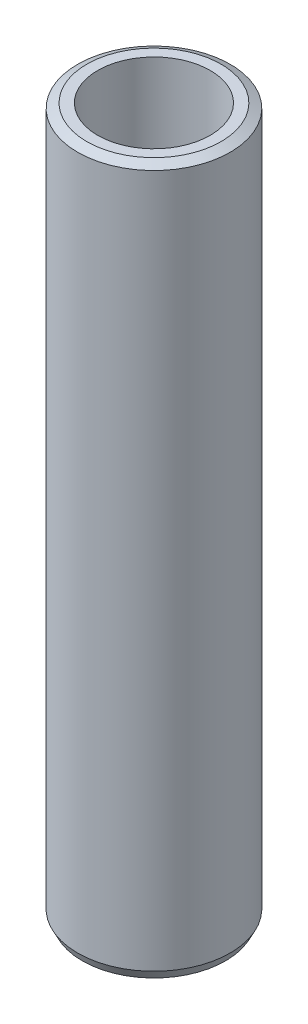
SolidWorks part; units mm, degrees
ref_plane "Front Plane" through (0, 0, 0) normal (0, 0, 1) x (1, 0, 0)
ref_plane "Top Plane" through (0, 0, 0) normal (0, 1, 0) x (1, 0, 0)
ref_plane "Right Plane" through (0, 0, 0) normal (1, 0, 0) x (0, 0, -1)
sketch "Sketch1" plane through (0, 0, 0) normal (0, 1, 0) x (1, 0, 0)
  circle A0 centre (0, 0) radius 35
  dimension "SHAFT_OD" = 70
extrude "Boss-Extrude1" add sketch "Sketch1" along normal blind 324.5434
sketch "Sketch2" plane through (0, 0, 0) normal (0, 1, 0) x (1, 0, 0)
  circle A0 centre (0, 0) radius 25.8207
  dimension "BORE_D" = 51.6414
extrude "Cut-Extrude1" cut sketch "Sketch2" along normal through all
chamfer "Chamfer1" distance 2.1415 angle 62.975 2 edges at (0, 324.5434, 35) (0, 0, 35) first distance on face at (0, 324.5434, 35) first distance on face at (0, 0, 25.8207)
